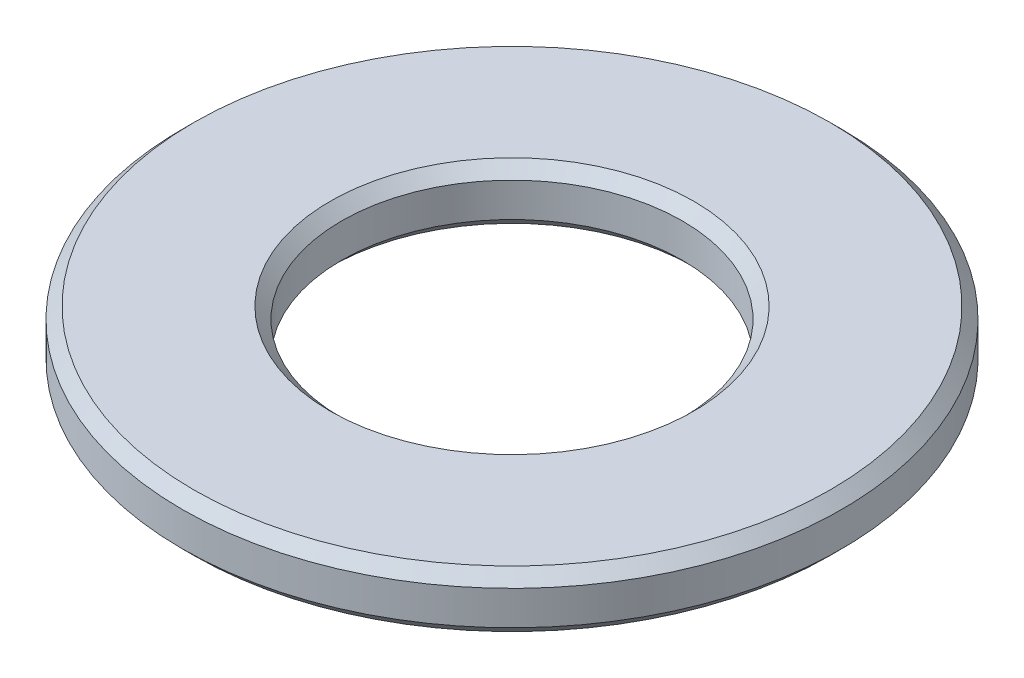
SolidWorks part; units mm, degrees
material "1.4000 (X6Cr13)"
ref_plane "Ebene vorne" through (0, 0, 0) normal (0, 0, 1) x (1, 0, 0)
ref_plane "Ebene oben" through (0, 0, 0) normal (0, 1, 0) x (1, 0, 0)
ref_plane "Ebene rechts" through (0, 0, 0) normal (1, 0, 0) x (0, 0, -1)
sketch "Skizze1" plane through (0, 0, 0) normal (0, 1, 0) x (1, 0, 0)
  circle A0 centre (0, 0) radius 1.5
  circle A1 centre (0, 0) radius 2.9
  dimension "D1" = 3
  dimension "D2" = 5.8
extrude "Aufsatz-Linear austragen1" add sketch "Skizze1" along normal blind 0.5
chamfer "Fase1" distance 0.1 angle 45 4 edges at (0, 0, 2.9) (0, 0, 1.5) (0, 0.5, 1.5) (0, 0.5, 2.9)
ref_axis "Achse1" through (0, -0.03, 0) along (0, 1, 0)
